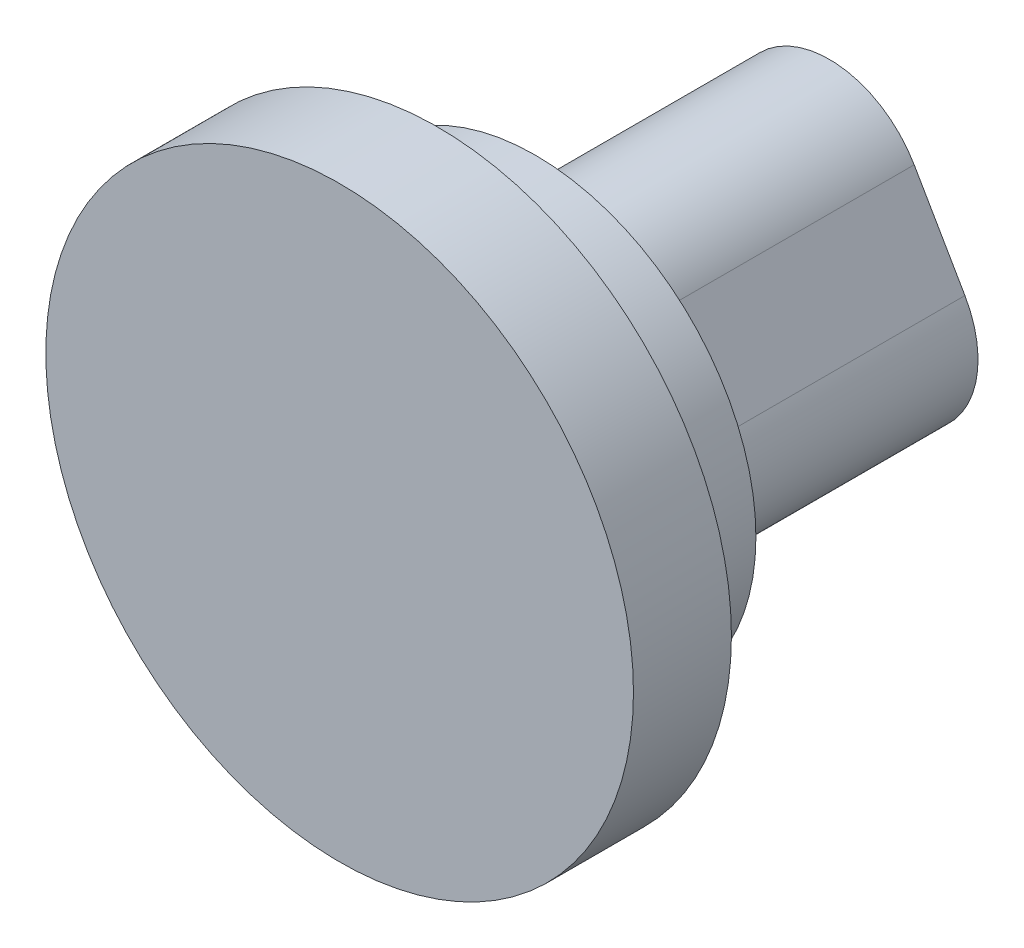
SolidWorks part; units mm, degrees
ref_plane "前视基准面" through (0, 0, 0) normal (0, 0, 1) x (1, 0, 0)
ref_plane "上视基准面" through (0, 0, 0) normal (0, 1, 0) x (1, 0, 0)
ref_plane "右视基准面" through (0, 0, 0) normal (1, 0, 0) x (0, 0, -1)
sketch "草图1" plane through (0, 0, 0) normal (0, 0, 1) x (1, 0, 0)
  line L0 (0, 0) -> (4.5, 0)
  line L1 (4.5, 0) -> (2.25, 3.8971)
  line L2 (2.25, 3.8971) -> (0, 0)
  dimension "D1" = 4.5
extrude "凸台-拉伸1" add sketch "草图1" along normal blind 3
sketch "草图2" plane through (0, 0, 3) normal (0, 0, 1) x (1, 0, 0)
  circle A0 centre (2.25, 1.299) radius 2.25
  dimension "D1" = 4.5
extrude "凸台-拉伸2" add sketch "草图2" along normal blind 1
sketch "草图3" plane through (0, 0, 4) normal (0, 0, 1) x (1, 0, 0)
  circle A0 centre (2.25, 1.299) radius 3
  dimension "D1" = 6
extrude "凸台-拉伸3" add sketch "草图3" along normal blind 1
fillet "圆角1" radius 1 3 edges at (0, 0, 1.5) (4.5, 0, 1.5) (2.25, 3.8971, 1.5)
